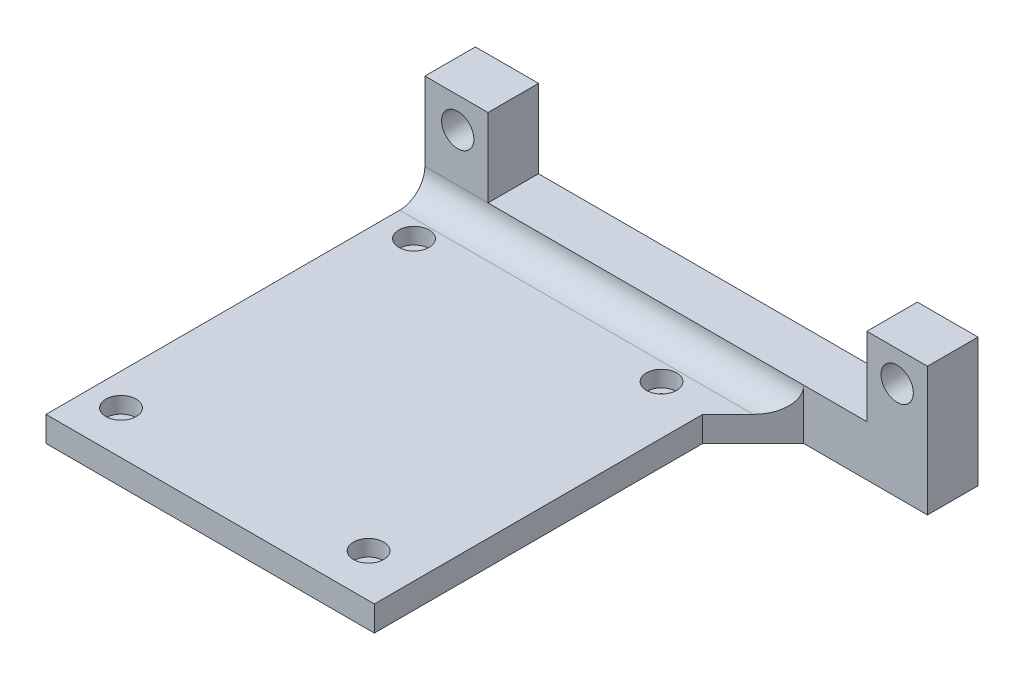
SolidWorks part; units mm, degrees
ref_plane "Front Plane" through (0, 0, 0) normal (0, 0, 1) x (1, 0, 0)
ref_plane "Top Plane" through (0, 0, 0) normal (0, 1, 0) x (1, 0, 0)
ref_plane "Right Plane" through (0, 0, 0) normal (1, 0, 0) x (0, 0, -1)
sketch "Sketch1" plane through (0, 0, 0) normal (0, 0, 1) x (1, 0, 0)
  line L0 (99.5, 3.2071) -> (99.5, 69.7929) construction
  line L1 (99.5, 12.5) -> (87.5, 12.5)
  line L2 (99.5, 12.5) -> (99.5, -13)
  line L3 (99.5, -13) -> (0, -13)
  line L4 (0, 12.5) -> (0, -13)
  line L5 (12.5, 12.5) -> (0, 12.5)
  line L7 (87.5, 12.5) -> (87.5, -3)
  line L8 (87.5, -3) -> (12.5, -3)
  line L9 (12.5, 12.5) -> (12.5, -3)
  line L12 (53.5, 0) -> (97, 0) construction
  line L13 (0, 70) -> (0, 3) construction
  line L14 (87.5, 30.5) -> (87.5, 0.5) construction
  line L15 (12.5, 0.5) -> (12.5, 30.5) construction
  circle A0 centre (93.5, 6.5) radius 3.2
  circle A1 centre (6.5, 6.5) radius 3.2
  point P24 (50, -3)
  dimension "D1" = 6.4
  dimension "D2" = 6.4
  dimension "D3" = 3
  dimension "D4" = 6
  dimension "D5" = 10
extrude "Boss-Extrude1" add sketch "Sketch1" along normal blind 10
sketch "Sketch2" plane through (0, 0, 10) normal (0, 0, 1) x (1, 0, 0)
  line L0 (0, -13) -> (99.5, -13) construction
  line L1 (0, -13) -> (65, -13)
  line L2 (0, -13) -> (0, -8)
  line L3 (0, -8) -> (65, -8)
  line L4 (65, -13) -> (65, -8)
  line L5 (35, -31.1318) -> (35, 49.1407) construction
  line L6 (0, 12.5) -> (0, -13) construction
  dimension "D1" = 65
  dimension "D2" = 30
  dimension "D3" = 35
  dimension "D4" = 5
extrude "Boss-Extrude2" add sketch "Sketch2" along normal blind 75
sketch "Sketch3" plane through (0, -13, 0) normal (0, -1, 0) x (1, 0, 0)
  line L0 (30.81, 1.0672) -> (30.81, 145.3953) construction
  circle A0 centre (6.31, 76.4577) radius 1.6
  circle A1 centre (55.31, 76.4577) radius 1.6
  circle A2 centre (6.31, 18.4577) radius 1.6
  circle A3 centre (55.31, 18.4577) radius 1.6
  arc A4 (6.31, 17.1577) -> (6.31, 19.7577) centre (6.31, 18.4577) ccw construction
  point P10 (0, 0)
  point P11 (48.9916, 1.0672)
  point P12 (55.31, 76.4577)
  dimension "D4" = 3.2
  dimension "D5" = 3.2
  dimension "D6" = 3.2
  dimension "D7" = 3.2
  dimension "D1" = 58
  dimension "D2" = 49
  dimension "D3" = 24.5
sketch "Sketch4" plane through (0, -13, 0) normal (0, -1, 0) x (1, 0, 0)
  circle A0 centre (6.31, 76.4577) radius 3
  circle A1 centre (55.31, 76.4577) radius 3
  circle A2 centre (55.31, 18.4577) radius 3
  circle A3 centre (6.31, 18.4577) radius 3
  dimension "D1" = 6
  dimension "D2" = 6
  dimension "D3" = 6
  dimension "D4" = 6
extrude "Boss-Extrude3" add sketch "Sketch4" along normal blind 3
extrude "Cut-Extrude1" cut sketch "Sketch4<2>" against normal up to next from offset 1.8 offset against normal yes
sketch "Sketch4<2>" plane through (0, -13, 0) normal (0, -1, 0) x (1, 0, 0) same geometry as "Sketch4"
extrude "Cut-Extrude2" cut sketch "Sketch3" against normal through all both and the other way through all
fillet "Fillet1" radius 5 1 edges at (32.5, -8, 10)
chamfer "Chamfer1" distance 10 angle 45 1 edges at (65, -8, 10)
fillet "Fillet2" radius 1.5 4 edges at (52.31, -13, 18.4577) (3.31, -13, 18.4577) (3.31, -13, 76.4577) (52.31, -13, 76.4577)
